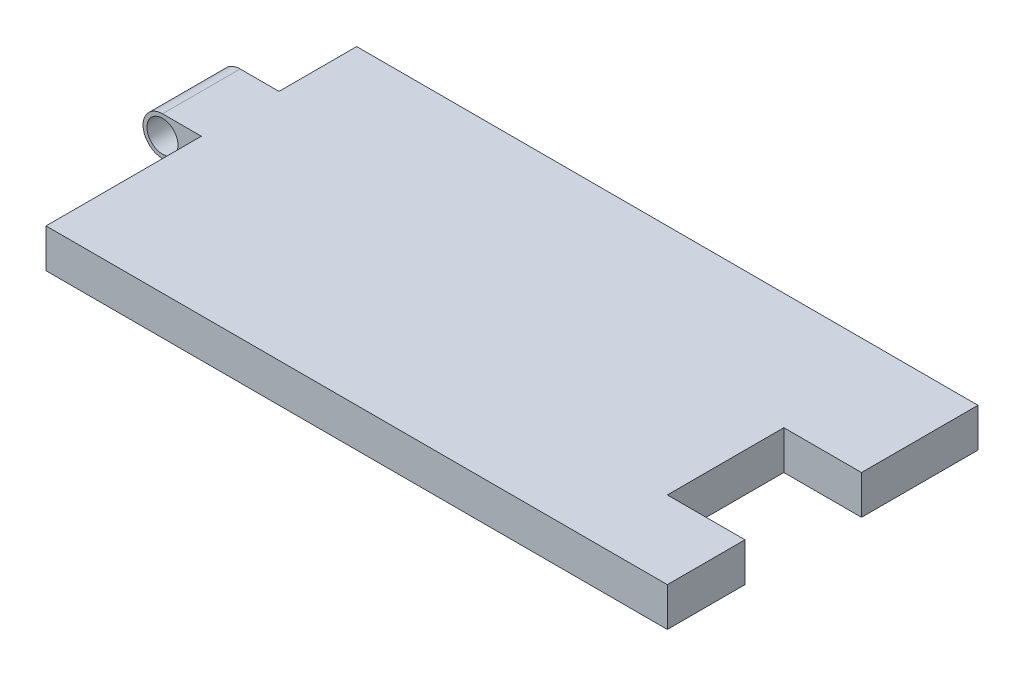
SolidWorks part; units mm, degrees
ref_plane "Plan de face" through (0, 0, 0) normal (0, 0, 1) x (1, 0, 0)
ref_plane "Plan de dessus" through (0, 0, 0) normal (0, 1, 0) x (1, 0, 0)
ref_plane "Plan de droite" through (0, 0, 0) normal (1, 0, 0) x (0, 0, -1)
sketch "Esquisse1" plane through (0, 0, 0) normal (0, 0, 1) x (1, 0, 0)
  line L0 (-80, 33.1442) -> (-80, -29.1403) construction
  line L5 (82.5, 15) -> (-82.5, -15) construction
  line L6 (82.5, -15) -> (-82.5, 15) construction
  line L7 (-88.7967, 0) -> (66.0295, 0) construction
  line L8 (-80, 2.5) -> (0, 2.5)
  line L9 (0, 2.5) -> (0, -2.5)
  line L10 (0, -2.5) -> (-80, -2.5)
  circle A0 centre (-80, 0) radius 2
  arc A1 (-80, 2.5) -> (-80, -2.5) centre (-80, 0) ccw
  point P0 (0, 0)
  dimension "D4" = 4
  dimension "D1" = 165
  dimension "D2" = 30
  dimension "D3" = 80
extrude "BASE" add sketch "Esquisse1" along normal blind 5 and the other way blind 5
sketch "Esquisse2" plane through (0, 0, 5) normal (0, 0, 1) x (1, 0, 0)
  line L0 (-75, 2.5) -> (-75, -2.5)
  line L1 (0, 2.5) -> (-80, 2.5) construction
  line L2 (-80, -2.5) -> (0, -2.5) construction
  line L3 (-75, -2.5) -> (0, -2.5)
  line L4 (0, -2.5) -> (0, 2.5)
  line L5 (0, 2.5) -> (-75, 2.5)
  dimension "D1" = 75
extrude "BOSS GRAND" add sketch "Esquisse2" along normal blind 10
sketch "Esquisse3" plane through (0, 0, -5) normal (0, 0, -1) x (-1, 0, 0)
  line L0 (0, 2.5) -> (0, -2.5)
  line L1 (0, -2.5) -> (75, -2.5)
  line L2 (80, -2.5) -> (0, -2.5) construction
  line L3 (75, -2.5) -> (75, 2.5)
  line L4 (0, 2.5) -> (80, 2.5) construction
  line L5 (75, 2.5) -> (0, 2.5)
  dimension "D1" = 75
extrude "BOSS PETIT" add sketch "Esquisse3" along normal blind 10
sketch "Esquisse4" plane through (0, 2.5, 0) normal (0, 1, 0) x (1, 0, 0)
  line L0 (0, 15) -> (5, 15)
  line L1 (5, 15) -> (5, 0)
  line L2 (5, 0) -> (0, 0)
  line L4 (0, 15) -> (0, 0)
  dimension "D1" = 5
extrude "BLOQUER" add sketch "Esquisse4" against normal blind 5
sketch "Esquisse5" plane through (0, 2.5, 0) normal (0, 1, 0) x (1, 0, 0)
  line L0 (0, 0) -> (-5, 0)
  line L1 (-5, 0) -> (-5, -15)
  line L2 (0, -15) -> (-75, -15) construction
  line L3 (-5, -15) -> (0, -15)
  line L4 (0, -15) -> (0, 0)
  dimension "D1" = 5
extrude "VIDE BLOQUER" cut sketch "Esquisse5" against normal blind 5
sketch "Esquisse6" plane through (0, 0, 15) normal (0, 0, 1) x (1, 0, 0)
  line L0 (5, -2.5) -> (5, 2.5) construction
  line L1 (-75, -2.5) -> (5, -2.5)
  line L2 (-75, -2.5) -> (-75, 2.5)
  line L3 (-75, 2.5) -> (5, 2.5)
  line L4 (5, -2.5) -> (5, 2.5)
  line L5 (-5, 2.5) -> (5, 2.5) construction
extrude "BOSSE BAS" add sketch "Esquisse6" along normal blind 10
sketch "Esquisse7" plane through (0, -2.5, 0) normal (0, -1, 0) x (1, 0, 0)
  line L0 (-10, -19.3005) -> (-10, 34.2683) construction
  line L1 (5, -15) -> (-75, -15) construction
  circle A0 centre (-10, -10) radius 2
  dimension "D3" = 4
  dimension "D1" = 10
  dimension "D2" = 5
extrude "Boss.-Extru.6" add sketch "Esquisse7" along normal blind 5
